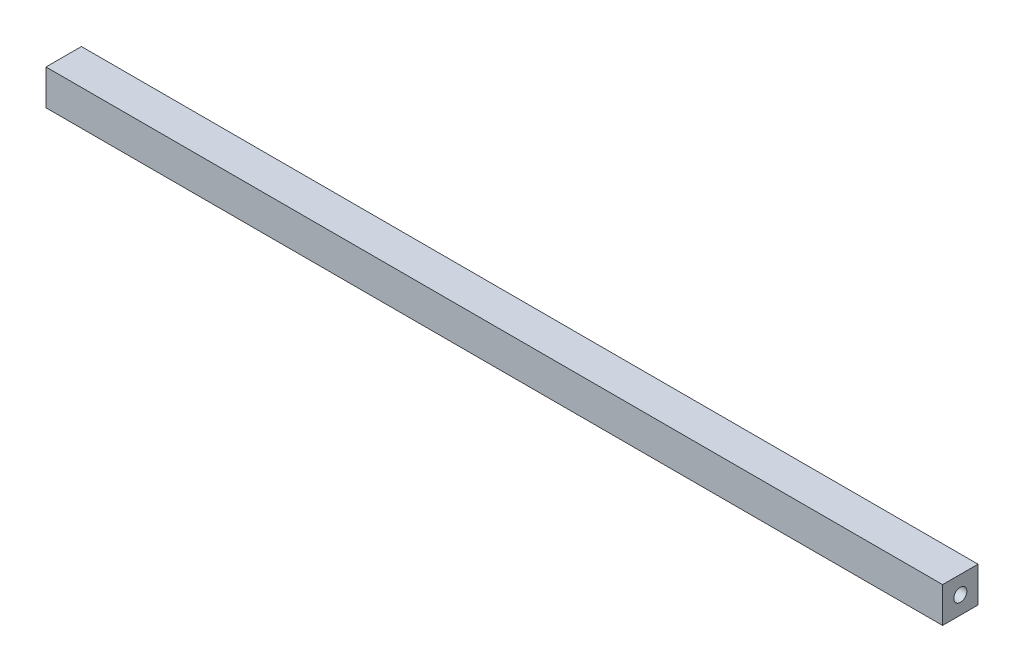
SolidWorks part; units mm, degrees
ref_plane "Front Plane" through (0, 0, 0) normal (0, 0, 1) x (1, 0, 0)
ref_plane "Top Plane" through (0, 0, 0) normal (0, 1, 0) x (1, 0, 0)
ref_plane "Right Plane" through (0, 0, 0) normal (1, 0, 0) x (0, 0, -1)
sketch "Sketch1" plane through (-17.272, 0, 0) normal (-1, 0, 0) x (0, 0, 1)
  line L1 (34.671, 91.821) -> (54.229, 91.821)
  line L2 (34.671, 91.821) -> (34.671, 111.379)
  line L3 (34.671, 111.379) -> (54.229, 111.379)
  line L4 (54.229, 91.821) -> (54.229, 111.379)
  line L5 (34.671, 91.821) -> (54.229, 111.379) construction
  line L6 (34.671, 111.379) -> (54.229, 91.821) construction
  point P0 (44.45, 101.6)
  dimension "D1" = 19.558
extrude "Boss-Extrude1" add sketch "Sketch1" along normal blind 457.2 and the other way blind 38.1 contours L3 L4 L1 L2
sketch "Sketch2" plane through (20.828, 0, 0) normal (1, 0, 0) x (0, 0, -1)
  circle A0 centre (-44.45, 101.6) radius 3.6195
  dimension "D1" = 7.239
extrude "Cut-Extrude1" cut sketch "Sketch2" against normal blind 38.1 contours A0
